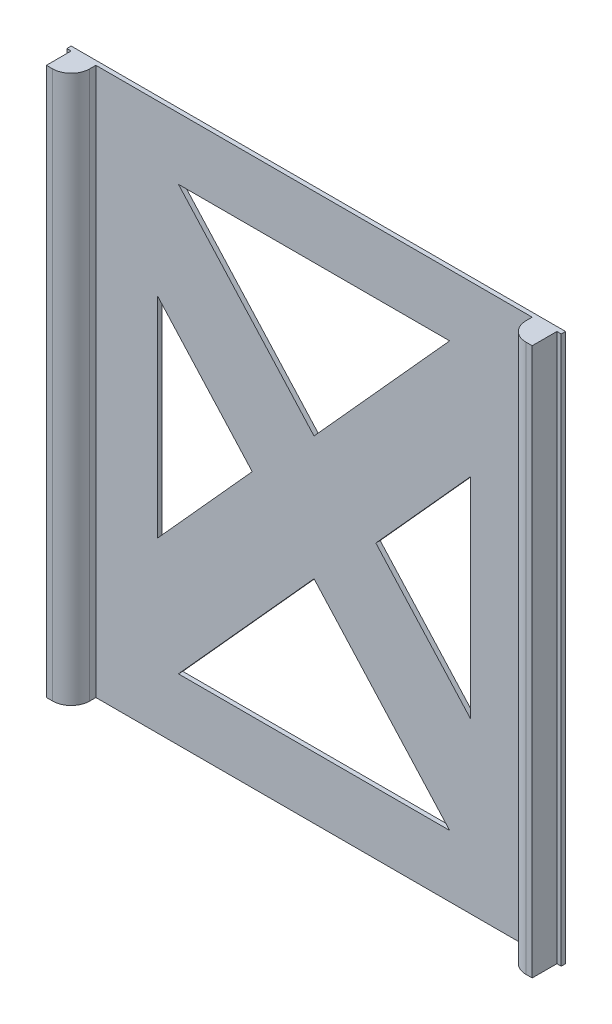
SolidWorks part; units mm, degrees
material "3.0205 (EN-AW 1200)"
ref_plane "Piano frontale" through (0, 0, 0) normal (0, 0, 1) x (1, 0, 0)
ref_plane "Piano superiore" through (0, 0, 0) normal (0, 1, 0) x (1, 0, 0)
ref_plane "Piano destro" through (0, 0, 0) normal (1, 0, 0) x (0, 0, -1)
sketch "Schizzo1" plane through (0, 0, 0) normal (0, 0, 1) x (1, 0, 0)
  line L1 (-400, -443) -> (400, -443)
  line L2 (-400, -443) -> (-400, 443)
  line L3 (-400, 443) -> (400, 443)
  line L4 (400, -443) -> (400, 443)
  line L5 (-400, -443) -> (400, 443) construction
  line L6 (-400, 443) -> (400, -443) construction
  point P0 (0, 0)
  dimension "D1" = 800
  dimension "D2" = 886
extrude "Estrusione-Estrusione1" add sketch "Schizzo1" along normal blind 7
sketch "Schizzo2" plane through (0, 0, 7) normal (0, 0, 1) x (1, 0, 0)
  line L0 (400, 443) -> (-400, 443) construction
  line L1 (-393, 443) -> (-353, 443)
  line L2 (-393, 443) -> (-393, -443)
  line L3 (-393, -443) -> (-353, -443)
  line L4 (-353, 443) -> (-353, -443)
  line L5 (-400, -443) -> (400, -443) construction
  line L6 (-400, 443) -> (-400, -443) construction
  dimension "D1" = 40
  dimension "D2" = 7
extrude "Estrusione-Estrusione2" add sketch "Schizzo2" along normal blind 40
fillet "Raccordo1" radius 30 1 edges at (-353, 0, 47)
mirror "Specchia1" about plane through (0, 0, 0) normal (1, 0, 0) of "Raccordo1", "Estrusione-Estrusione2"
sketch "Schizzo3" plane through (0, 0, 7) normal (0, 0, 1) x (1, 0, 0)
  line L0 (-400, 443) -> (400, -443) construction
  line L1 (-400, -443) -> (400, 443) construction
  line L2 (0, 443) -> (0, -443) construction
  line L3 (353, 443) -> (-353, 443) construction
  line L4 (-353, -443) -> (353, -443) construction
  line L6 (400, -443) -> (400, 443) construction
  line L7 (400, 0) -> (-393, 0) construction
  line L8 (-393, 443) -> (-393, -443) construction
  line L11 (-100, 0) -> (-253, 169.4475)
  line L12 (-253, 169.4475) -> (-253, -169.4475)
  line L13 (-253, -169.4475) -> (-100, 0)
  line L14 (253, 169.4475) -> (253, -169.4475)
  line L15 (253, -169.4475) -> (100, 0)
  line L16 (100, 0) -> (253, 169.4475)
  line L17 (219.4131, -343) -> (0, -100)
  line L18 (0, -100) -> (-219.4131, -343)
  line L19 (-219.4131, -343) -> (219.4131, -343)
  line L20 (353, -443) -> (353, 443) construction
  line L21 (-400, 443) -> (-400, -443) construction
  line L22 (-353, -443) -> (-353, 443) construction
  line L23 (-219.4131, 343) -> (219.4131, 343)
  line L24 (219.4131, 343) -> (0, 100)
  line L25 (0, 100) -> (-219.4131, 343)
  point P31 (0, -343)
  point P33 (253, 0)
  point P34 (-253, 0)
  point P35 (0, 0)
  point P42 (0, 343)
  point P44 (0, 0)
  dimension "D1" = 100
  dimension "D2" = 100
  dimension "D3" = 100
  dimension "D4" = 100
  dimension "D5" = 100
  dimension "D6" = 100
  dimension "D7" = 100
  dimension "D8" = 100
extrude "Taglio-Estrusione1" cut sketch "Schizzo3" against normal through all
